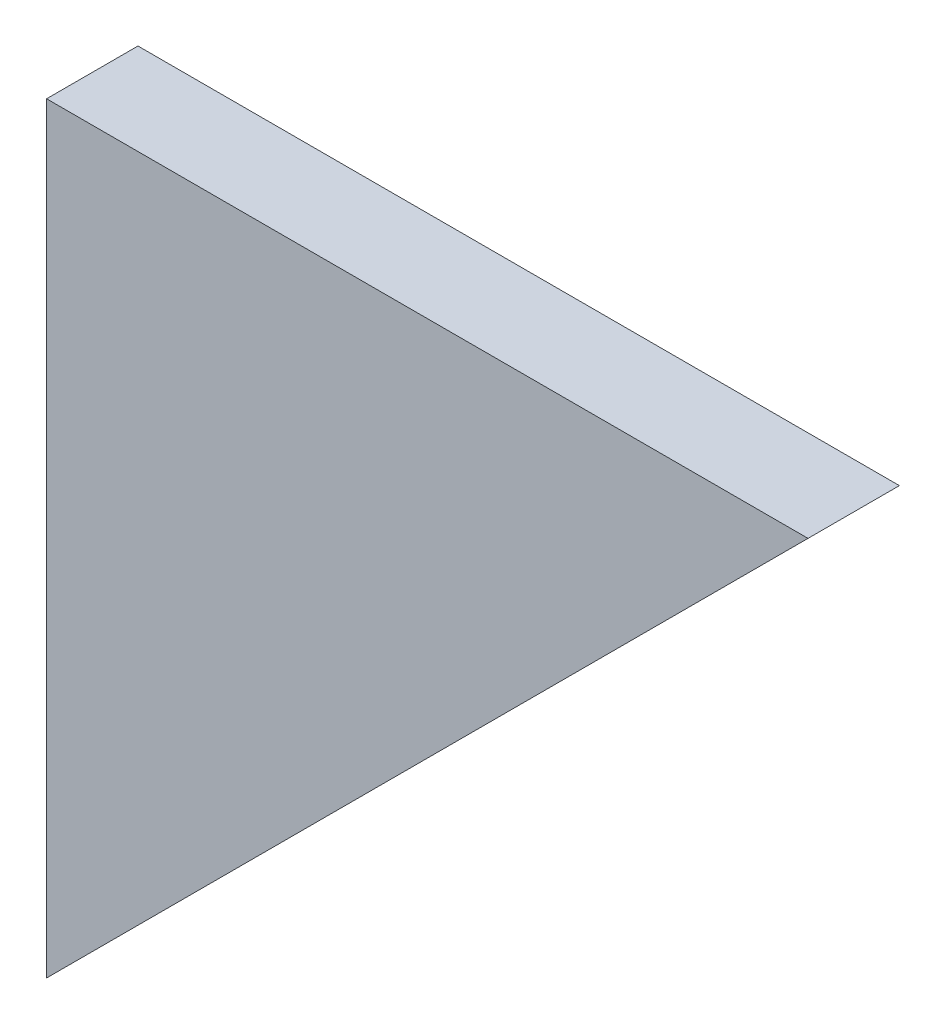
SolidWorks part; units mm, degrees
material "Клен"
ref_plane "Спереди" through (0, 0, 0) normal (0, 0, 1) x (1, 0, 0)
ref_plane "Сверху" through (0, 0, 0) normal (0, 1, 0) x (1, 0, 0)
ref_plane "Справа" through (0, 0, 0) normal (1, 0, 0) x (0, 0, -1)
sketch "Эскиз1" plane through (0, 0, 0) normal (0, 0, 1) x (1, 0, 0)
  line L5 (6, -293.8462) -> (6, -343.8462)
  line L7 (6, -343.8462) -> (56, -293.8462)
  line L9 (56, -293.8462) -> (6, -293.8462)
  dimension "D1" = 50
  dimension "D2" = 50
extrude "Бобышка-Вытянуть1" add sketch "Эскиз1" against normal blind 6 contours L7 L9 L5
